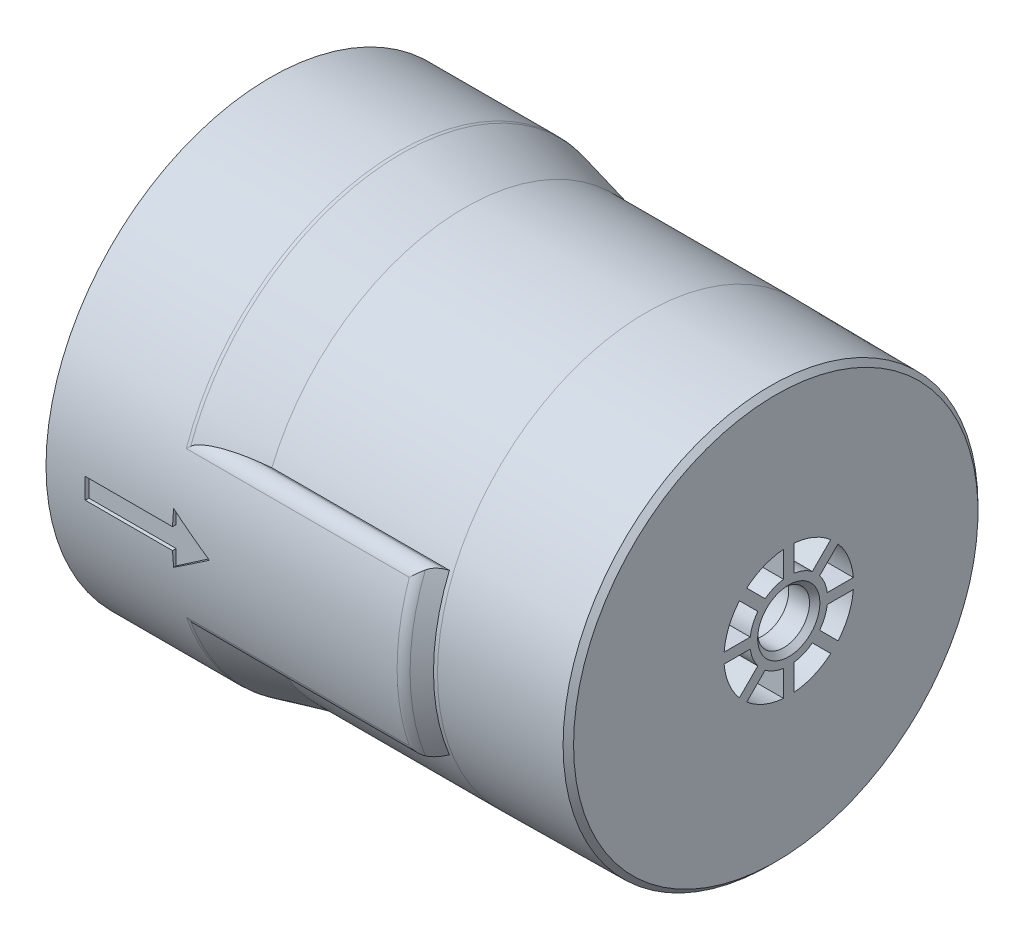
SolidWorks part; units mm, degrees
ref_plane "Front Plane" through (0, 0, 0) normal (0, 0, 1) x (1, 0, 0)
ref_plane "Top Plane" through (0, 0, 0) normal (0, 1, 0) x (1, 0, 0)
ref_plane "Right Plane" through (0, 0, 0) normal (1, 0, 0) x (0, 0, -1)
sketch "Sketch1" plane through (0, 0, 0) normal (0, 0, 1) x (1, 0, 0)
  line L0 (-80.1124, 0) -> (69.6237, 0) construction
  line L1 (-80.2087, 17.3) -> (-70.2087, 17.3)
  line L2 (-70.2087, 17.3) -> (-65.2087, 16.1)
  line L3 (-65.2087, 16.1) -> (-51.2087, 16.1)
  line L4 (-80.2087, 16.1) -> (-70.2092, 16.1)
  line L5 (-70.2092, 16.1) -> (-65.2092, 14.9)
  line L6 (-65.2092, 14.9) -> (-45.2092, 14.9)
  line L7 (-80.2087, 17.3) -> (-80.2087, 16.1)
  line L8 (-45.2092, 14.9) -> (-45.2092, 0)
  line L9 (-45.2092, 0) -> (-41.2092, 0)
  line L10 (-41.2092, 0) -> (-41.2092, 16)
  line L11 (-41.2092, 16) -> (-51.2087, 16.1)
  line L12 (-70.2087, 17.3) -> (-70.2092, 16.1) construction
  dimension "D2" = 10
  dimension "D3" = 16.1
  dimension "D4" = 10
  dimension "D5" = 14
  dimension "D6" = 5
  dimension "D7" = 16.1
  dimension "D8" = 41.2092
  dimension "D9" = 20
  dimension "D1" = 4
  dimension "D10" = 5
  dimension "D11" = 16
  dimension "D12" = 1.2
  dimension "D13" = 1.2
revolve "Revolve1" add sketch "Sketch1" angle 360 about L0
sketch "Sketch2" plane through (-41.2092, 0, 0) normal (1, 0, 0) x (0, 0, -1)
  line L0 (1, 0) -> (-21.0341, 0) construction
  line L1 (-3.984, 0.4) -> (-3.482, 0.4)
  line L3 (1, 0) -> (-21.0341, 0) construction
  line L10 (1, 0) -> (-16.203, 17.203) construction
  line L11 (-1.3852, 1.8195) -> (-1.9187, 2.353)
  line L12 (-3.482, 0.4) -> (-1.9732, 0.4)
  line L13 (-1.9187, 2.353) -> (-2.807, 3.2414)
  line L14 (0.6, 3.7276) -> (0.6, 4.984)
  line L15 (-2.2414, 3.807) -> (-1.8864, 3.4521)
  line L16 (0.6, 2.9732) -> (0.6, 3.7276)
  line L17 (-1.8864, 3.4521) -> (-0.8195, 2.3852)
  line L18 (3.353, 2.9187) -> (4.2414, 3.807)
  line L19 (1.4, 4.984) -> (1.4, 4.482)
  line L20 (2.8195, 2.3852) -> (3.353, 2.9187)
  line L21 (1.4, 4.482) -> (1.4, 2.9732)
  line L22 (4.7276, 0.4) -> (5.984, 0.4)
  line L23 (4.807, 3.2414) -> (4.4521, 2.8864)
  line L24 (3.9732, 0.4) -> (4.7276, 0.4)
  line L25 (4.4521, 2.8864) -> (3.3852, 1.8195)
  line L26 (3.9187, -2.353) -> (4.807, -3.2414)
  line L27 (5.984, -0.4) -> (5.482, -0.4)
  line L28 (3.3852, -1.8195) -> (3.9187, -2.353)
  line L29 (5.482, -0.4) -> (3.9732, -0.4)
  line L30 (1.4, -3.7276) -> (1.4, -4.984)
  line L31 (4.2414, -3.807) -> (3.8864, -3.4521)
  line L32 (1.4, -2.9732) -> (1.4, -3.7276)
  line L33 (3.8864, -3.4521) -> (2.8195, -2.3852)
  line L34 (-1.353, -2.9187) -> (-2.2414, -3.807)
  line L35 (0.6, -4.984) -> (0.6, -4.482)
  line L36 (-0.8195, -2.3852) -> (-1.353, -2.9187)
  line L37 (0.6, -4.482) -> (0.6, -2.9732)
  line L38 (-2.7276, -0.4) -> (-3.984, -0.4)
  line L39 (-2.807, -3.2414) -> (-2.4521, -2.8864)
  line L40 (-1.9732, -0.4) -> (-2.7276, -0.4)
  line L41 (-2.4521, -2.8864) -> (-1.3852, -1.8195)
  circle A9 centre (0, 0) radius 16 construction
  arc A11 (-1.9732, 0.4) -> (-1.3852, 1.8195) centre (1, 0) cw
  arc A15 (-3.984, 0.4) -> (-2.807, 3.2414) centre (1, 0) cw
  arc A18 (-2.2414, 3.807) -> (0.6, 4.984) centre (1, 0) cw
  arc A21 (-0.8195, 2.3852) -> (0.6, 2.9732) centre (1, 0) cw
  arc A22 (1.4, 4.984) -> (4.2414, 3.807) centre (1, 0) cw
  arc A25 (1.4, 2.9732) -> (2.8195, 2.3852) centre (1, 0) cw
  arc A26 (4.807, 3.2414) -> (5.984, 0.4) centre (1, 0) cw
  arc A29 (3.3852, 1.8195) -> (3.9732, 0.4) centre (1, 0) cw
  arc A30 (5.984, -0.4) -> (4.807, -3.2414) centre (1, 0) cw
  arc A33 (3.9732, -0.4) -> (3.3852, -1.8195) centre (1, 0) cw
  arc A34 (4.2414, -3.807) -> (1.4, -4.984) centre (1, 0) cw
  arc A37 (2.8195, -2.3852) -> (1.4, -2.9732) centre (1, 0) cw
  arc A38 (0.6, -4.984) -> (-2.2414, -3.807) centre (1, 0) cw
  arc A41 (0.6, -2.9732) -> (-0.8195, -2.3852) centre (1, 0) cw
  arc A42 (-2.807, -3.2414) -> (-3.984, -0.4) centre (1, 0) cw
  arc A45 (-1.3852, -1.8195) -> (-1.9732, -0.4) centre (1, 0) cw
  point P11 (1, 0)
  point P27 (2, 0)
  point P74 (1, 0)
  dimension "D2" = 0.4
  dimension "D4" = 3
  dimension "D8" = 5
  dimension "D9" = 8
  dimension "D1" = 45
  dimension "D3" = 0.4
  dimension "D5" = 1
ref_plane "Plane1" through (0, 0, 12) normal (0, 0, 1) x (1, 0, 0)
extrude "Cut-Extrude5" cut sketch "Sketch2" against normal up to next
ref_plane "Plane3" through (0, 0, -1) normal (0, 0, -1) x (-1, 0, 0)
sketch "Sketch8" plane through (0, 0, -1) normal (0, 0, -1) x (-1, 0, 0)
  line L0 (41.4715, 0) -> (64.2594, 0) construction
  line L1 (45.2092, -2.5) -> (43.2092, -2.5)
  line L2 (41.2092, 16) -> (41.2092, -16) construction
  line L3 (45.2092, -2.5) -> (45.2092, 0)
  line L4 (41.2092, -2) -> (41.2092, 0)
  line L5 (45.2092, 0) -> (41.2092, 0)
  line L6 (43.2092, -2.5) -> (43.2092, -2)
  line L7 (43.2092, -2) -> (41.2092, -2)
  dimension "D1" = 2.5
  dimension "D2" = 2
  dimension "D3" = 4
  dimension "D4" = 2
revolve "Cut-Revolve2" cut sketch "Sketch8" angle 360 about L0
chamfer "Chamfer1" distance 0.4 angle 45 3 edges at (-41.2092, 0, 16) (-80.2087, 0, 16.1) (-41.2092, 0, -3) first distance on face at (-41.2092, 0, -3) first distance on face at (-80.2087, 0, 16.1)
fillet "Fillet4" radius 10 1 edges at (-70.2092, 0, 16.1)
sketch "Sketch12" plane through (0, 0, 0) normal (0, 1, 0) x (1, 0, 0)
  line L0 (-38.7859, 0) -> (-87.7556, 0) construction
  line L1 (-51.5117, -16.103) -> (-65.2087, -16.1)
  line L3 (-70.2087, -17.3) -> (-52.7087, -17.3)
  line L4 (-70.2092, 17.2) -> (-65.2092, 16)
  line L5 (-65.2087, -16.1) -> (-70.2087, -17.3)
  line L6 (-65.2087, -16.1) -> (-70.2087, -17.3)
  line L7 (-52.7087, -17.3) -> (-51.5117, -16.103)
  line L8 (-65.2092, 16) -> (-41.2092, 16)
  line L9 (-41.6132, -16.004) -> (-51.2087, -16.1)
  line L10 (-41.6132, -16.004) -> (-51.2087, -16.1) construction
  dimension "D1" = 17.5
  dimension "D2" = 45
revolve "Revolve2" add sketch "Sketch12" angle 45 mid plane about L0 region at (-59.976, 0, 16.7251)
ref_plane "Plane4" through (0, 0, 17) normal (0, 0, 1) x (1, 0, 0)
sketch "Sketch13" plane through (0, 0, 17) normal (0, 0, 1) x (1, 0, 0)
  line L0 (-77.1995, 0.799) -> (-70.4645, 0.799)
  line L1 (-70.4645, 1.958) -> (-70.4645, 0.799)
  line L2 (-70.4645, 1.958) -> (-67.6061, 0)
  line L3 (-77.1995, 0.799) -> (-77.1995, -0.799)
  line L4 (-66.0568, 0) -> (-78.8911, 0) construction
  line L5 (-77.1995, -0.799) -> (-70.4645, -0.799)
  line L6 (-70.4645, -1.958) -> (-70.4645, -0.799)
  line L7 (-70.4645, -1.958) -> (-67.6061, 0)
  point P10 (-77.1995, 0)
extrude "Cut-Extrude6" cut sketch "Sketch13" along normal blind 1.2
fillet "Fillet7" radius 1 4 edges at (-61.4587, 6.6204, 15.9831) (-52.7087, 0, 17.3) (-61.4587, -6.6204, 15.9831) (-70.2087, 0, -17.3)
sketch "Sketch3" plane through (0, 0, 12) normal (0, 0, 1) x (1, 0, 0)
  line L6 (-65.8174, 16.2461) -> (-65.8174, -16.2461) construction
  line L7 (-65.8174, 10.2323) -> (-41.2092, 10.2323)
  line L8 (-65.8174, 10.2323) -> (-65.8174, -10.138)
  line L9 (-65.8174, -10.138) -> (-41.2092, -10.138)
  line L10 (-41.2092, 10.2323) -> (-41.2092, -10.138)
  line L11 (-41.2092, -16) -> (-41.2092, 16) construction
extrude "Boss-Extrude1" add sketch "Sketch3" along normal up to body separate body
sketch "Sketch4" plane through (0, 0, 12) normal (0, 0, 1) x (1, 0, 0)
  line L0 (-65.8174, 16.2461) -> (-65.8174, -16.2461) construction
  line L2 (-71.1934, 0) -> (-58.0618, 0) construction
  circle A0 centre (-60.8174, 0) radius 2
  dimension "D2" = 4
  dimension "D1" = 5
extrude "Cut-Extrude2" [suppressed] cut sketch "Sketch4" along normal up to next
ref_plane "Plane2" through (0, 0, 12.8) normal (0, 0, 1) x (1, 0, 0)
sketch "Sketch5" [suppressed] plane through (0, 0, 12.8) normal (0, 0, 1) x (1, 0, 0)
  circle A0 centre (-60.8174, 0) radius 3
  dimension "D1" = 6
extrude "Cut-Extrude4" [suppressed] cut sketch "Sketch5" along normal through all
fillet "Fillet2" radius 2 2 edges at (-55.2092, 8.8323, 12) (-55.2092, -8.8323, 12)
fillet "Fillet9" radius 1 1 edges at (-65.8174, 0, 12)
fillet "Fillet12" radius 0.4 4 edges at (-45.2092, 8.8198, 11.8842) (-45.2092, 0, 12) (-45.2092, -8.8198, 11.8842) (-45.2092, 0, -14.9)
